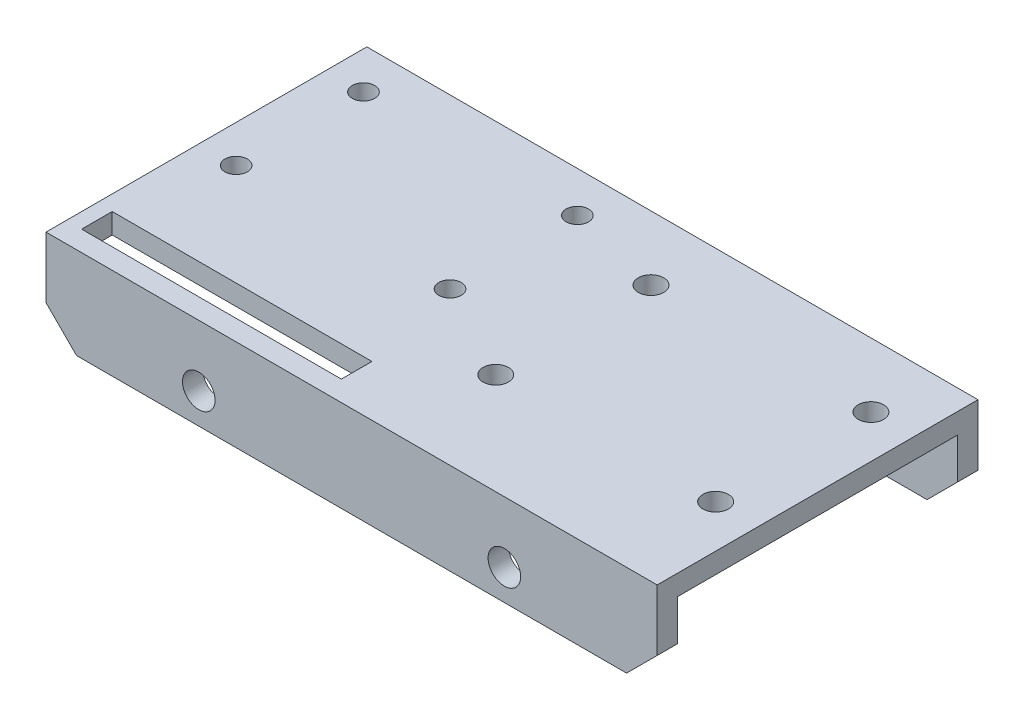
SolidWorks part; units mm, degrees
ref_plane "Front Plane" through (0, 0, 0) normal (0, 0, 1) x (1, 0, 0)
ref_plane "Top Plane" through (0, 0, 0) normal (0, 1, 0) x (1, 0, 0)
ref_plane "Right Plane" through (0, 0, 0) normal (1, 0, 0) x (0, 0, -1)
sketch "Sketch1" plane through (0, 0, 0) normal (0, 1, 0) x (1, 0, 0)
  line L1 (-30, 15.75) -> (30, 15.75)
  line L2 (-30, 15.75) -> (-30, -15.75)
  line L3 (-30, -15.75) -> (30, -15.75)
  line L4 (30, 15.75) -> (30, -15.75)
  line L5 (-30, 15.75) -> (30, -15.75) construction
  line L6 (-30, -15.75) -> (30, 15.75) construction
  point P0 (0, 0)
  dimension "D1" = 31.5
  dimension "D2" = 60
extrude "Boss-Extrude1" add sketch "Sketch1" along normal blind 2
sketch "Sketch2" plane through (0, 0, 0) normal (0, -1, 0) x (1, 0, 0)
  line L0 (-30, -15.75) -> (-30, 15.75) construction
  line L1 (30, -15.75) -> (-30, -15.75)
  line L2 (30, -15.75) -> (30, -13.75)
  line L3 (30, -13.75) -> (-30, -13.75)
  line L4 (-30, -15.75) -> (-30, -13.75)
  line L6 (30, 15.75) -> (-30, 15.75)
  line L7 (30, 15.75) -> (30, 13.75)
  line L8 (30, 13.75) -> (-30, 13.75)
  line L9 (-30, 15.75) -> (-30, 13.75)
  dimension "D1" = 2
  dimension "D2" = 2
extrude "Boss-Extrude2" add sketch "Sketch2" along normal blind 7
sketch "Sketch3" plane through (0, 0, -15.75) normal (0, 0, -1) x (-1, 0, 0)
  line L0 (0, -7) -> (0, 2) construction
  line L1 (30, -7) -> (-30, -7) construction
  line L2 (-30, 2) -> (30, 2) construction
  line L3 (30, -7) -> (0, -7) construction
  line L4 (15, -7) -> (15, 2) construction
  circle A0 centre (15, -4) radius 1.6
  circle A1 centre (-15, -4) radius 1.6
  dimension "D1" = 3.2
  dimension "D2" = 3
extrude "Cut-Extrude1" cut sketch "Sketch3" against normal through all both and the other way through all
chamfer "Chamfer1" distance 3 angle 45 2 edges at (-30, -7, -14.75) (30, -7, -14.75)
chamfer "Chamfer3" distance 3 angle 45 2 edges at (30, -7, 14.75) (-30, -7, 14.75)
sketch "Sketch4" plane through (0, 2, 0) normal (0, 1, 0) x (1, 0, 0)
  circle A0 centre (25.795, -5.801) radius 1.25 construction
  circle A1 centre (4.205, -5.801) radius 1.25 construction
  circle A2 centre (25.795, 9.439) radius 1.25 construction
  circle A3 centre (4.205, 9.439) radius 1.25 construction
  circle A4 centre (-26.335, -0.75) radius 1.1 construction
  circle A5 centre (-26.335, 11.75) radius 1.1 construction
  circle A6 centre (-5.335, -0.75) radius 1.1 construction
  circle A7 centre (-5.335, 11.75) radius 1.1 construction
  circle A8 centre (25.795, -5.801) radius 1.25
  circle A9 centre (4.205, -5.801) radius 1.25
  circle A10 centre (25.795, 9.439) radius 1.25
  circle A11 centre (4.205, 9.439) radius 1.25
  circle A12 centre (-26.335, -0.75) radius 1.1
  circle A13 centre (-26.335, 11.75) radius 1.1
  circle A14 centre (-5.335, -0.75) radius 1.1
  circle A15 centre (-5.335, 11.75) radius 1.1
extrude "Cut-Extrude2" cut sketch "Sketch4" against normal blind 10
sketch "Sketch5" plane through (0, 0, 0) normal (0, -1, 0) x (1, 0, 0)
  line L0 (-30, -13.75) -> (-30, 13.75) construction
  line L1 (-28.5, 13.75) -> (-3, 13.75)
  line L2 (-28.5, 13.75) -> (-28.5, 10.75)
  line L3 (-28.5, 10.75) -> (-3, 10.75)
  line L4 (-3, 13.75) -> (-3, 10.75)
  line L5 (-30, 13.75) -> (30, 13.75) construction
  dimension "D1" = 1.5
  dimension "D2" = 25.5
  dimension "D3" = 3
  dimension "D4" = 0
extrude "Cut-Extrude3" cut sketch "Sketch5" against normal blind 10
equation "\"D2@Sketch2\"=\"D1@Sketch2\""
